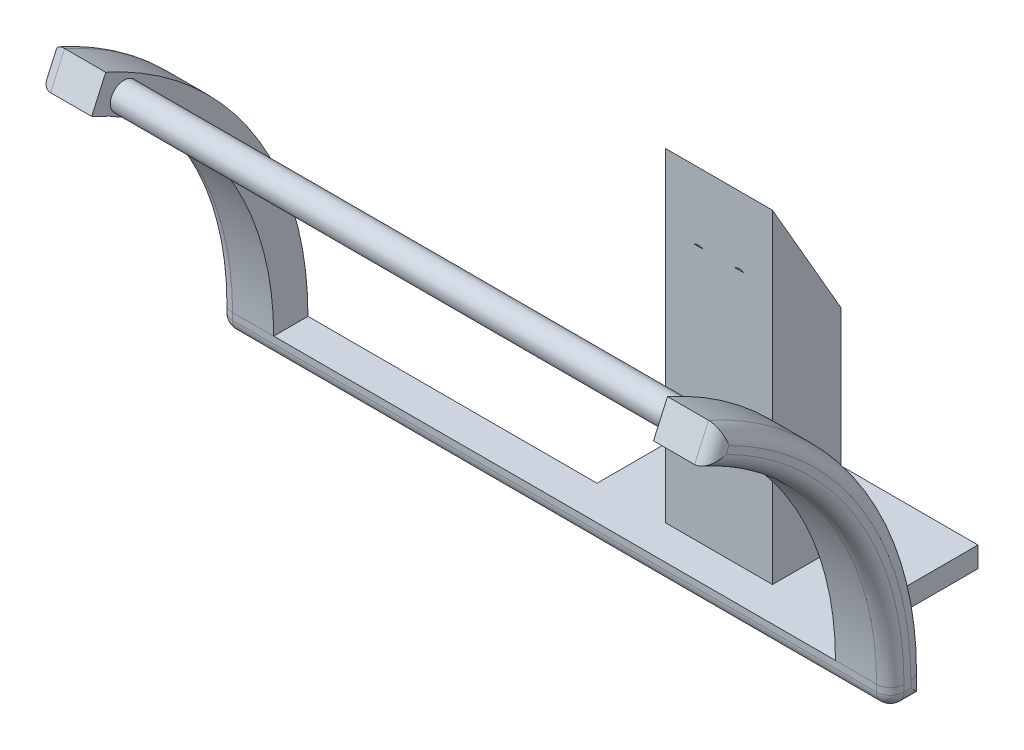
SolidWorks part; units mm, degrees
ref_plane "Front Plane" through (0, 0, 0) normal (0, 0, 1) x (1, 0, 0)
ref_plane "Top Plane" through (0, 0, 0) normal (0, 1, 0) x (1, 0, 0)
ref_plane "Right Plane" through (0, 0, 0) normal (1, 0, 0) x (0, 0, -1)
sketch "Sketch1" plane through (0, 0, 0) normal (0, 1, 0) x (1, 0, 0)
  line L0 (-8.4368, 20.25) -> (-8.4368, 0.25) construction
  line L1 (-26.2418, 20.25) -> (9.3682, 20.25)
  line L2 (-26.2418, 20.25) -> (-26.2418, 0.25)
  line L3 (-26.2418, 0.25) -> (9.3682, 0.25)
  line L4 (9.3682, 20.25) -> (9.3682, 0.25)
  line L5 (-38.4368, 0.25) -> (21.5632, 0.25)
  line L6 (-38.4368, 0.25) -> (-38.4368, -4.75)
  line L7 (-38.4368, -4.75) -> (21.5632, -4.75)
  line L8 (21.5632, 0.25) -> (21.5632, -4.75)
  line L9 (-23.1313, 20.25) -> (6.2616, 20.25) construction
  line L11 (-38.4368, -4.75) -> (-76.4368, -4.75)
  line L12 (-38.4368, -4.75) -> (-38.4368, 0.25)
  line L13 (-38.4368, 0.25) -> (-76.4368, 0.25)
  line L14 (-76.4368, -4.75) -> (-76.4368, 0.25)
  point P10 (-8.4368, 0.25)
  dimension "D1" = 20
  dimension "D2" = 35.61
  dimension "D3" = 60
  dimension "D4" = 5
  dimension "D5" = 38
extrude "Boss-Extrude1" add sketch "Sketch1" along normal blind 3 contours L8 L5 L3 L6 L7 | L1 L0 L5 L4 | L0 L1 L2 L3 | L12 L11 L14 L13 region at (0.4657, 0, -10.25) region at (-17.3393, 0, -10.25) region at (-8.4368, 0, 2.25)
ref_plane "Plane1" through (21.5632, 0, 0) normal (1, 0, 0) x (0, 0, -1)
sketch "Sketch2" plane through (21.5632, 0, 0) normal (1, 0, 0) x (0, 0, -1)
  line L0 (-4.75, 3) -> (-34.75, 3) construction
  line L1 (-34.75, 3) -> (-49.75, 3) construction
  line L2 (-29.2678, 48.6123) -> (-31.316, 44.051)
  line L3 (-4.75, 3) -> (0.25, 3)
  circle A0 centre (-49.75, 3) radius 15 construction
  arc A1 (-4.75, 3) -> (-31.316, 44.051) centre (-49.75, 3) ccw
  arc A2 (0.25, 3) -> (-29.2678, 48.6123) centre (-49.75, 3) ccw
  dimension "D3" = 30
  dimension "D1" = 30
  dimension "D2" = 15
ref_plane "Plane2" through (-8.4368, 0, 0) normal (1, 0, 0) x (0, 0, -1)
sketch "Sketch3" plane through (0, 0, 0) normal (0, -1, 0) x (1, 0, 0)
  circle A0 centre (-20.4847, -8.75) radius 1.5
  circle A1 centre (-8.4349, -16.25) radius 1.5
  circle A2 centre (3.6149, -8.75) radius 1.5
  dimension "D1" = 3
extrude "Cut-Extrude1" cut sketch "Sketch3" against normal blind 5
sketch "Sketch7" plane through (0, 3, 0) normal (0, 1, 0) x (1, 0, 0)
  line L0 (-26.2418, 20.25) -> (-26.2418, 0.25) construction
  line L1 (-16.2418, 10.25) -> (-0.6318, 10.25)
  line L2 (-16.2418, 10.25) -> (-16.2418, 0.25)
  line L3 (-16.2418, 0.25) -> (-0.6318, 0.25)
  line L4 (-0.6318, 10.25) -> (-0.6318, 0.25)
  line L5 (9.3682, 20.25) -> (9.3682, 0.25) construction
  line L6 (-38.4368, -4.75) -> (21.5632, -4.75) construction
  dimension "D1" = 10
  dimension "D2" = 10
  dimension "D3" = 5
  dimension "D4" = 10
extrude "Boss-Extrude4" add sketch "Sketch7" along normal blind 30
sketch "Sketch8" plane through (-16.2418, 0, 0) normal (-1, 0, 0) x (0, 0, 1)
  line L0 (-10.25, 33) -> (-0.25, 50.3205)
  line L1 (-0.25, 33) -> (-0.25, 50.3205)
  line L2 (-10.25, 33) -> (-0.25, 33) construction
  line L3 (-10.25, 33) -> (-0.25, 33)
  dimension "D1" = 60
extrude "Boss-Extrude5" add sketch "Sketch8" against normal up to surface (15.61 mm away) up to face at (-0.6318, 18, -5.25)
sketch "Sketch9" plane through (0, 12.6884, -21.9769) normal (0, 0.5, -0.866) x (1, 0, 0)
  line L0 (-16.2418, -33.4538) -> (-0.6318, -33.4538) construction
  line L1 (-16.2418, -43.4538) -> (-16.2418, -23.4538) construction
  line L2 (-0.6318, -23.4538) -> (-0.6318, -43.4538) construction
  line L3 (-8.4368, -23.4538) -> (-8.4368, -43.4538) construction
  line L4 (-0.6318, -23.4538) -> (-16.2418, -23.4538) construction
  line L5 (-0.6318, -43.4538) -> (-16.2418, -43.4538) construction
  circle A0 centre (-11.4368, -33.4538) radius 1.5
  circle A1 centre (-5.4368, -33.4538) radius 1.5
  dimension "D1" = 3
  dimension "D2" = 3
  dimension "D3" = 6
  dimension "D4" = 3
extrude "Cut-Extrude2" cut sketch "Sketch9" against normal blind 5
extrude "Boss-Extrude6" add sketch "Sketch2" against normal blind 8
ref_plane "Plane3" through (-27.4368, 0, 0) normal (-1, 0, 0) x (0, 0, 1)
mirror "Mirror1" about plane through (-27.4368, 0, 0) normal (-1, 0, 0) of "Boss-Extrude6"
fillet "Fillet4" radius 2 13 edges at (-76.4368, 1.5, -0.25) (-76.4368, 30.1651, 7.7732) (-76.4368, 46.3317, 30.2919) (-76.4368, 27.4486, 11.9708) (-76.4368, 1.5, 4.75) (-76.4368, 0, 2.25) (21.5632, 1.5, 4.75) (21.5632, 27.4486, 11.9708) (21.5632, 46.3317, 30.2919) (21.5632, 30.1651, 7.7732) (21.5632, 1.5, -0.25) (21.5632, 0, 2.25) (-27.4368, 0, 4.75)
sketch "Sketch10" plane through (-68.4368, 0, 0) normal (1, 0, 0) x (0, 0, -1)
  line L0 (-21.8913, 44.5198) -> (-23.9724, 39.8852)
  line L1 (-31.316, 44.051) -> (-21.8913, 44.5198) construction
  line L2 (-4.75, 3) -> (0.25, 3)
  line L3 (-29.2678, 48.6123) -> (-31.316, 44.051)
  line L4 (-4.75, 3) -> (0.25, 3)
  line L5 (-29.2678, 48.6123) -> (-31.316, 44.051)
  line L6 (-23.9724, 39.8852) -> (-29.2678, 48.6123) construction
  circle A0 centre (-26.6036, 44.2854) radius 2
  arc A2 (-4.75, 3) -> (-31.316, 44.051) centre (-49.75, 3) ccw
  arc A3 (0.25, 3) -> (-29.2678, 48.6123) centre (-49.75, 3) ccw
  arc A4 (-4.75, 3) -> (-31.316, 44.051) centre (-49.75, 3) ccw
  arc A5 (0.25, 3) -> (-29.2678, 48.6123) centre (-49.75, 3) ccw
  dimension "D2" = 4
  dimension "D1" = 0
extrude "Boss-Extrude7" add sketch "Sketch10" along normal up to surface (82 mm away) contours A0 region at (-68.4368, 44.2854, 26.6036) up to face at (13.5632, 26.7364, 13.0715)
